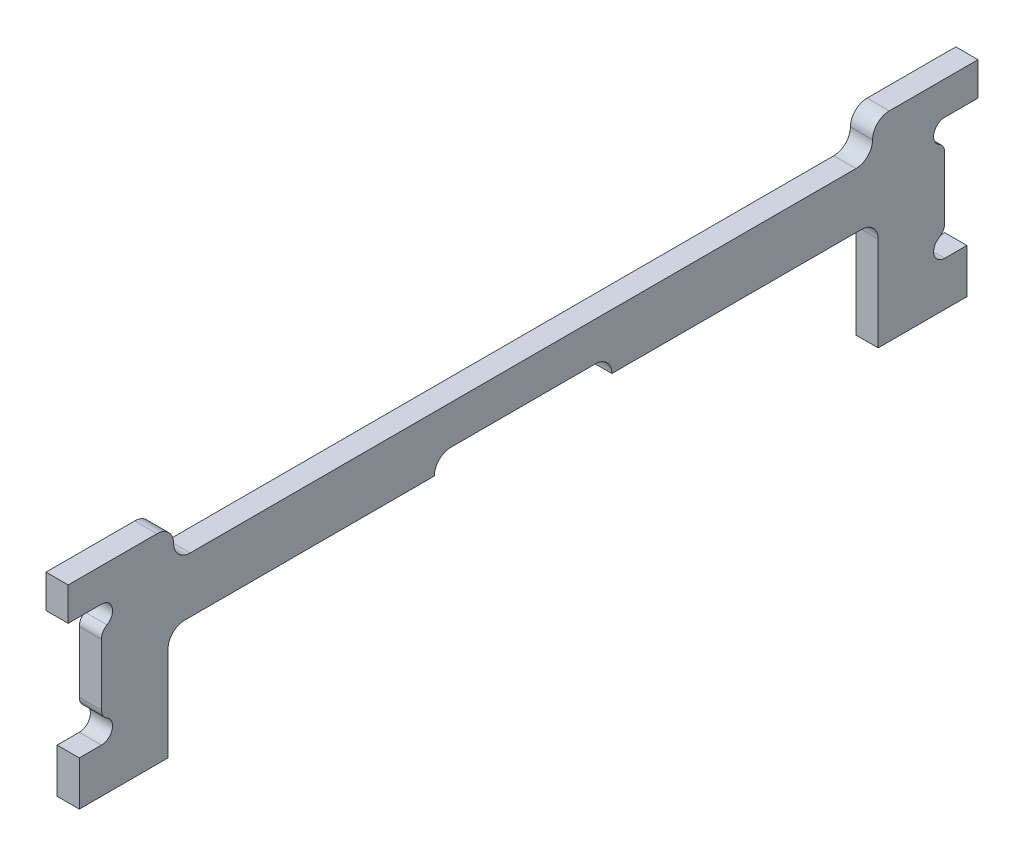
SolidWorks part; units mm, degrees
material "Thornel Mat VMA"
ref_plane "前视基准面" through (0, 0, 0) normal (0, 0, 1) x (1, 0, 0)
ref_plane "上视基准面" through (0, 0, 0) normal (0, 1, 0) x (1, 0, 0)
ref_plane "右视基准面" through (0, 0, 0) normal (1, 0, 0) x (0, 0, -1)
sketch "草图1" plane through (0, 0, 0) normal (1, 0, 0) x (0, 0, -1)
  line L0 (0, 0) -> (0, 23.9263) construction
  line L1 (32, -10) -> (32, 0)
  line L4 (32, 0) -> (0, 0)
  line L5 (32, -10) -> (38, -10)
  line L8 (0, 0) -> (0, 5)
  line L9 (38, 5) -> (41, 5)
  line L10 (41, 5) -> (41, 8)
  line L11 (41, 8) -> (31.5, 8)
  line L12 (38, 5) -> (38, -10)
  line L13 (31.5, 8) -> (31.5, 5)
  line L14 (31.5, 5) -> (0, 5)
  dimension "D1" = 6
  dimension "D2" = 32
  dimension "D3" = 10
  dimension "D4" = 5
  dimension "D5" = 15
  dimension "D6" = 3
  dimension "D7" = 0.5
  dimension "D8" = 3
extrude "凸台-拉伸1" add sketch "草图1" along normal blind 2
sketch "草图3" plane through (2, 0, 0) normal (1, 0, 0) x (0, 0, -1)
  line L1 (38, -10) -> (40, -10)
  line L2 (38, -10) -> (38, -6)
  line L3 (38, -6) -> (40, -6)
  line L4 (40, -10) -> (40, -6)
  dimension "D1" = 4
  dimension "D2" = 2
extrude "凸台-拉伸2" add sketch "草图3" against normal up to surface (2 mm away) up to face at (0, 1.6, -28.5)
mirror "镜向1" about plane through (0, 0, 0) normal (0, 0, 1) of "凸台-拉伸2", "凸台-拉伸1"
sketch "草图4" plane through (2, 0, 0) normal (1, 0, 0) x (0, 0, -1)
  line L0 (-32, 0) -> (32, 0) construction
  line L1 (-8, -1.5) -> (8, -1.5)
  line L2 (-8, -1.5) -> (-8, 1.5)
  line L3 (-8, 1.5) -> (8, 1.5)
  line L4 (8, -1.5) -> (8, 1.5)
  line L5 (-8, -1.5) -> (8, 1.5) construction
  line L6 (-8, 1.5) -> (8, -1.5) construction
  point P0 (0, 0)
  dimension "D1" = 1.5
  dimension "D2" = 16
extrude "切除-拉伸1" cut sketch "草图4" against normal blind 10
fillet "圆角1" radius 1.5 2 edges at (1, 1.5, -8) (1, 1.5, 8)
sketch "草图5" plane through (2, 0, 0) normal (1, 0, 0) x (0, 0, -1)
  line L0 (-38, -6) -> (-38, 5) construction
  line L1 (0, 0) -> (0, -8.0571) construction
  circle A0 centre (-38, 4) radius 1
  circle A1 centre (-38, -5) radius 1
  circle A2 centre (38, -5) radius 1
  circle A3 centre (38, 4) radius 1
  dimension "D1" = 2
  dimension "D2" = 2
extrude "切除-拉伸2" cut sketch "草图5" against normal blind 10
fillet "圆角2" radius 1 4 edges at (1, -4, -38) (1, 3, -38) (1, -4, 38) (1, 3, 38)
fillet "圆角3" radius 1.5 6 edges at (1, 0, 32) (1, 0, -32) (1, 5, -31.5) (1, 8, -31.5) (1, 5, 31.5) (1, 8, 31.5)
